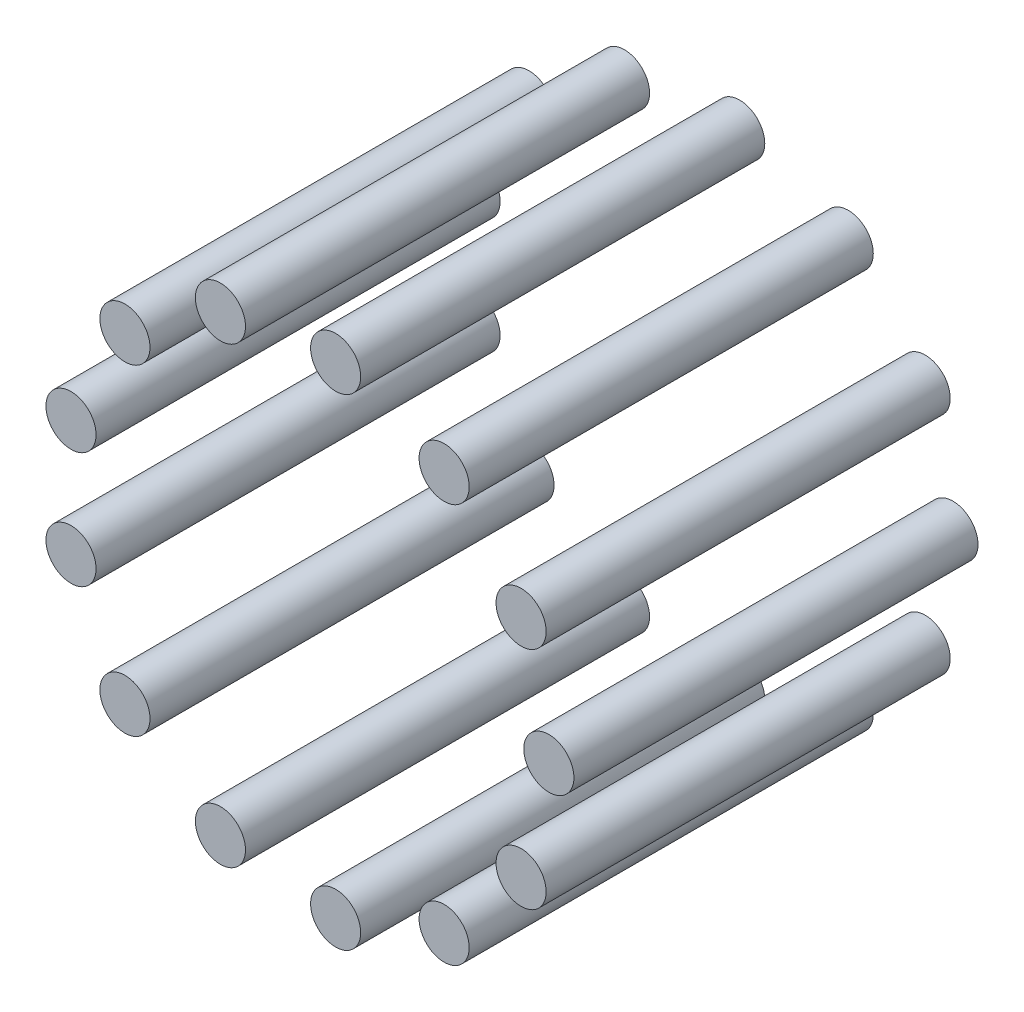
SolidWorks part; units mm, degrees
ref_plane "Front Plane" through (0, 0, 0) normal (0, 0, 1) x (1, 0, 0)
ref_plane "Top Plane" through (0, 0, 0) normal (0, 1, 0) x (1, 0, 0)
ref_plane "Right Plane" through (0, 0, 0) normal (1, 0, 0) x (0, 0, -1)
sketch "Sketch1" plane through (0, 0, 0) normal (0, 0, 1) x (1, 0, 0)
  line L0 (30, 0) -> (-28.8858, 0) construction
  line L1 (26.5637, 13.9417) -> (0, 0) construction
  circle A0 centre (0, 0) radius 30 construction
  circle A1 centre (30, 0) radius 3.1
  circle A2 centre (26.5637, -13.9417) radius 3.1
  circle A3 centre (17.0419, -24.6895) radius 3.1
  circle A4 centre (3.6161, -29.7813) radius 3.1
  circle A5 centre (-10.6381, -28.0505) radius 3.1
  circle A6 centre (-22.4553, -19.8937) radius 3.1
  circle A7 centre (-29.1283, -7.1795) radius 3.1
  circle A8 centre (-29.1283, 7.1795) radius 3.1
  circle A9 centre (-22.4553, 19.8937) radius 3.1
  circle A10 centre (-10.6381, 28.0505) radius 3.1
  circle A11 centre (3.6161, 29.7813) radius 3.1
  circle A12 centre (17.0419, 24.6895) radius 3.1
  circle A13 centre (26.5637, 13.9417) radius 3.1
  point P32 (0, 0)
  dimension "D1" = 6.2
  dimension "D3" = 60
  dimension "D4" = 27.692
  dimension "D2" = 13
extrude "Boss-Extrude1" add sketch "Sketch1" along normal blind 50
